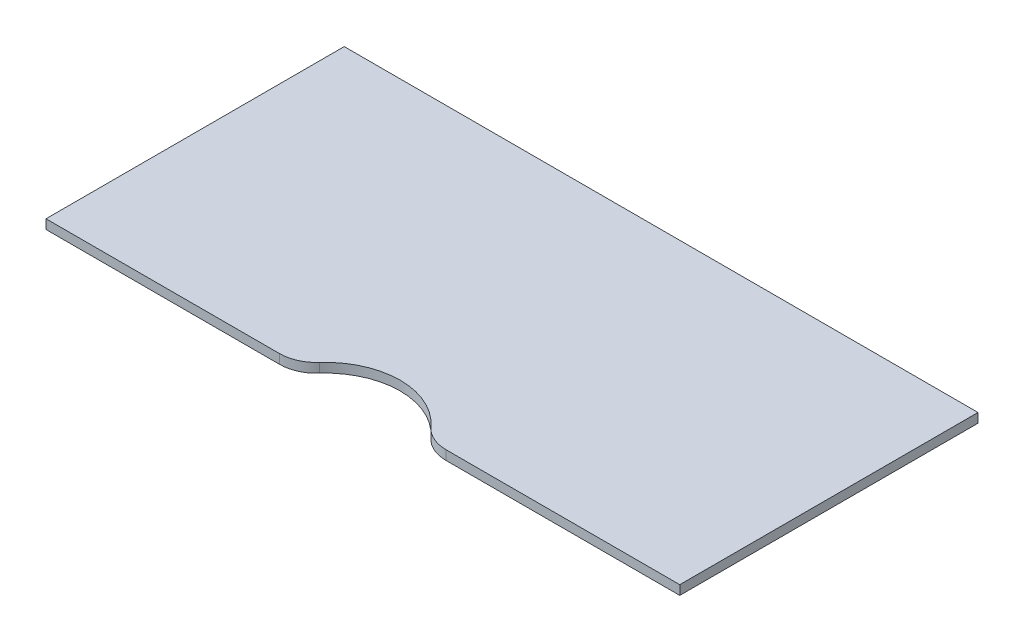
SolidWorks part; units mm, degrees
ref_plane "Front Plane" through (0, 0, 0) normal (0, 0, 1) x (1, 0, 0)
ref_plane "Top Plane" through (0, 0, 0) normal (0, 1, 0) x (1, 0, 0)
ref_plane "Right Plane" through (0, 0, 0) normal (1, 0, 0) x (0, 0, -1)
sketch "Sketch1" plane through (0, 0, 0) normal (0, 1, 0) x (1, 0, 0)
  line L0 (0, 101.6) -> (0, 0)
  line L1 (0, 0) -> (215.9, 0)
  line L2 (0, 0) -> (0, 228.6)
  line L3 (0, 228.6) -> (215.9, 228.6)
  line L4 (215.9, 0) -> (215.9, 228.6)
  line L5 (0, 127) -> (85.953, 127)
  line L6 (0, 127) -> (0, 101.6)
  line L7 (0, 101.6) -> (85.953, 101.6)
  line L8 (85.953, 127) -> (85.953, 101.6)
  line L9 (215.9, 127) -> (129.947, 127)
  line L10 (215.9, 127) -> (215.9, 101.6)
  line L11 (215.9, 101.6) -> (129.947, 101.6)
  line L12 (129.947, 127) -> (129.947, 101.6)
  line L13 (215.9, 0) -> (215.9, 101.6)
  circle A0 centre (107.95, 114.3) radius 25.4
  point P13 (85.953, 114.3)
  point P18 (0, 114.3)
  dimension "D4" = 50.8
  dimension "D5" = 85.953
  dimension "D1" = 228.6
  dimension "D2" = 215.9
  dimension "D3" = 25.4
extrude "Boss-Extrude1" add sketch "Sketch1" along normal blind 3.175 contours A0 L9 L4 L3 L2 L5 region at (107.95, 0, -178.6387)
fillet "Fillet1" radius 12.7 2 edges at (129.947, 1.5875, -127) (85.953, 1.5875, -127)
